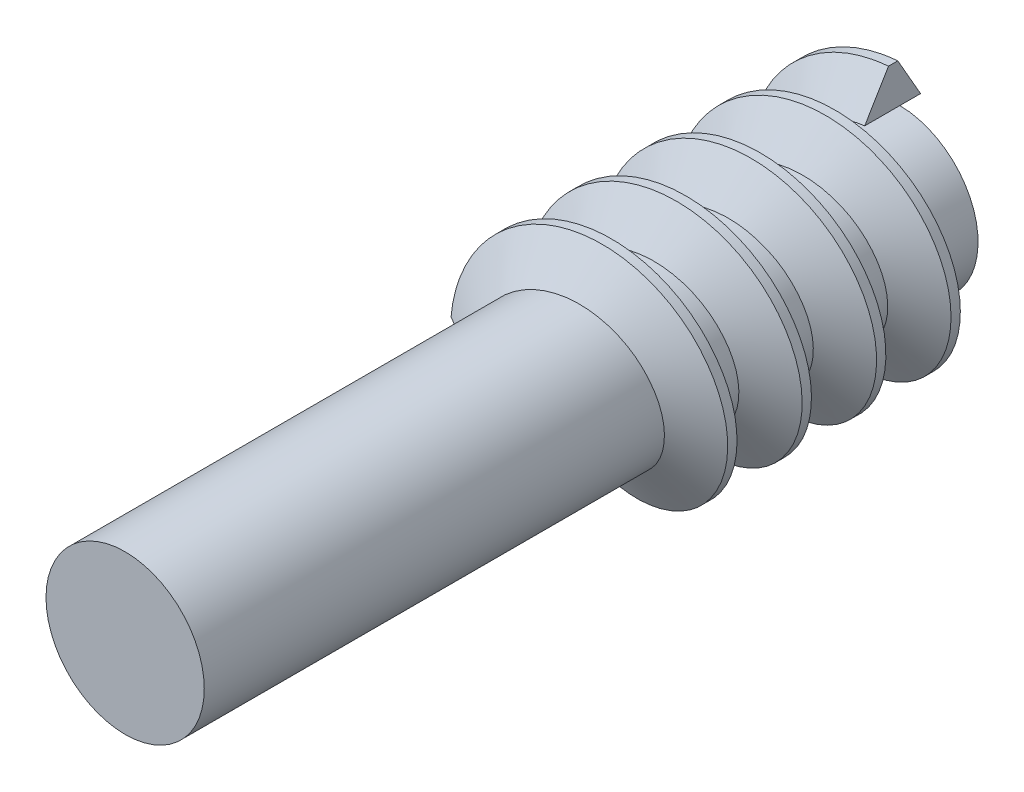
SolidWorks part; units mm, degrees
ref_plane "Front Plane" through (0, 0, 0) normal (0, 0, 1) x (1, 0, 0)
ref_plane "Top Plane" through (0, 0, 0) normal (0, 1, 0) x (1, 0, 0)
ref_plane "Right Plane" through (0, 0, 0) normal (1, 0, 0) x (0, 0, -1)
sketch "Sketch1" plane through (0, 0, 0) normal (0, 0, 1) x (1, 0, 0)
  circle A0 centre (0, 0) radius 2.25
  dimension "D1" = 4.5
extrude "Boss-Extrude1" add sketch "Sketch1" along normal blind 10
thread "Thread1" pitch 2.1167 method extrude profile "Thread Profile1" start angle 0, offset 0, length 9, pitch 2.1167, diameter 4.5
ref_plane "Plane1" through (-2.25, 0, 10) normal (0, -1, 0) x (-1, 0, 0)
sketch "Thread Profile1" plane through (-2.25, 0, 10) normal (0, -1, 0) x (-1, 0, 0)
  line L0 (0, 0) -> (0, 2.1167) construction
  line L1 (0, 0) -> (1.1457, 0.6615)
  line L2 (1.1457, 0.6615) -> (1.1457, 0.926)
  line L3 (1.1457, 0.926) -> (0, 1.5875)
  line L4 (1.1457, 0.7937) -> (0, 0.7937) construction
  line L11 (0, 0) -> (0, 1.5875)
  point P2 (0, 0)
  dimension "Pitch" = 2.1167
  dimension "Profile_Angle" = 60
  dimension "Profile_Land" = 0.2646
  dimension "Profile_Height" = 1.1457
sketch "Sketch4" plane through (0, 0, 10) normal (0, 0, 1) x (1, 0, 0)
  circle A0 centre (0, 0) radius 2.25
  dimension "D1" = 4.5
extrude "Boss-Extrude2" add sketch "Sketch4" along normal blind 12
